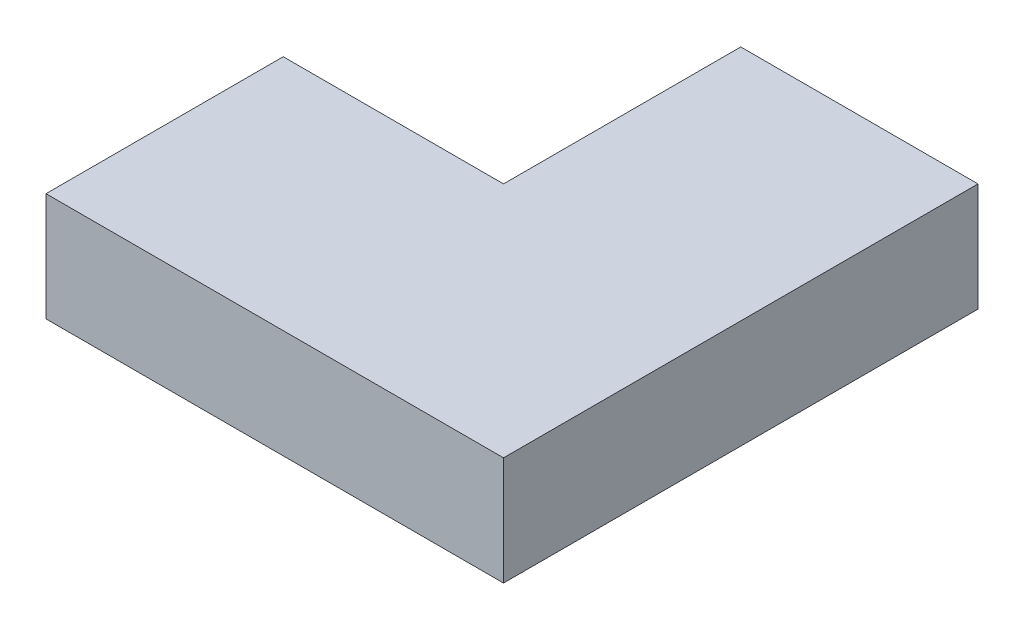
SolidWorks part; units mm, degrees
ref_plane "Front Plane" through (0, 0, 0) normal (0, 0, 1) x (1, 0, 0)
ref_plane "Top Plane" through (0, 0, 0) normal (0, 1, 0) x (1, 0, 0)
ref_plane "Right Plane" through (0, 0, 0) normal (1, 0, 0) x (0, 0, -1)
sketch "Sketch2" plane through (0, 0, 0) normal (0, -1, 0) x (1, 0, 0)
  line L0 (-13.7962, 46.5082) -> (-13.7962, -23.4918)
  line L1 (-13.7962, 46.5082) -> (-104.2962, 46.5082)
  line L2 (-13.7962, -23.4918) -> (-48.7962, -23.4918)
  line L4 (-104.2962, 46.5082) -> (-104.2962, 11.5082)
  line L5 (-104.2962, 11.5082) -> (-48.7962, 11.5082)
  line L6 (-48.7962, 11.5082) -> (-48.7962, -23.4918)
  dimension "D1" = 70
  dimension "D2" = 90.5
  dimension "D3" = 35
  dimension "D4" = 35
extrude "Boss-Extrude1" add sketch "Sketch2" along normal mid plane 16
other "Move Face1" flip direction yes face at (-104.2962, 0, 29.0082) offset 23 parameters "D1"=23
